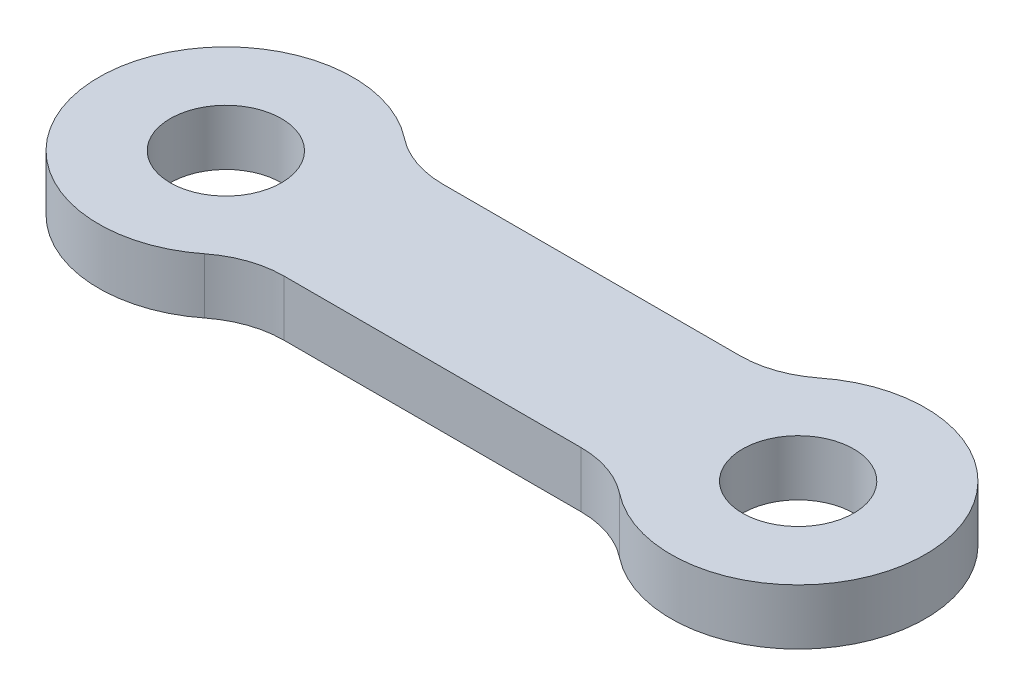
SolidWorks part; units mm, degrees
ref_plane "Front Plane" through (0, 0, 0) normal (0, 0, 1) x (1, 0, 0)
ref_plane "Top Plane" through (0, 0, 0) normal (0, 1, 0) x (1, 0, 0)
ref_plane "Right Plane" through (0, 0, 0) normal (1, 0, 0) x (0, 0, -1)
sketch "Sketch1" plane through (0, 0, 0) normal (0, 1, 0) x (1, 0, 0)
  line L0 (0, 0) -> (18, 0) construction
  line L1 (3.1225, 2.5) -> (14.8775, 2.5)
  line L2 (3.1225, -2.5) -> (14.8775, -2.5)
  circle A0 centre (0, 0) radius 4
  circle A1 centre (18, 0) radius 4
  circle A2 centre (0, 0) radius 1.75
  circle A3 centre (18, 0) radius 1.75
  dimension "D1" = 8
  dimension "D3" = 8
  dimension "D5" = 3.5
  dimension "D6" = 3.5
  dimension "D2" = 18
  dimension "D4" = 2.5
extrude "Boss-Extrude1" add sketch "Sketch1" along normal blind 1.75 contours A2 A0 | L0 A0 L2 A1 | A0 L0 A1 L1 | A1 A3 region at (3.6675, 0, 1.2873) region at (9, 0, -1.2837) region at (9, 0, 1.2837) region at (14.3325, 0, -1.2873)
fillet "Fillet1" radius 3 4 edges at (3.1225, 0.875, 2.5) (14.8775, 0.875, 2.5) (14.8775, 0.875, -2.5) (3.1225, 0.875, -2.5)
